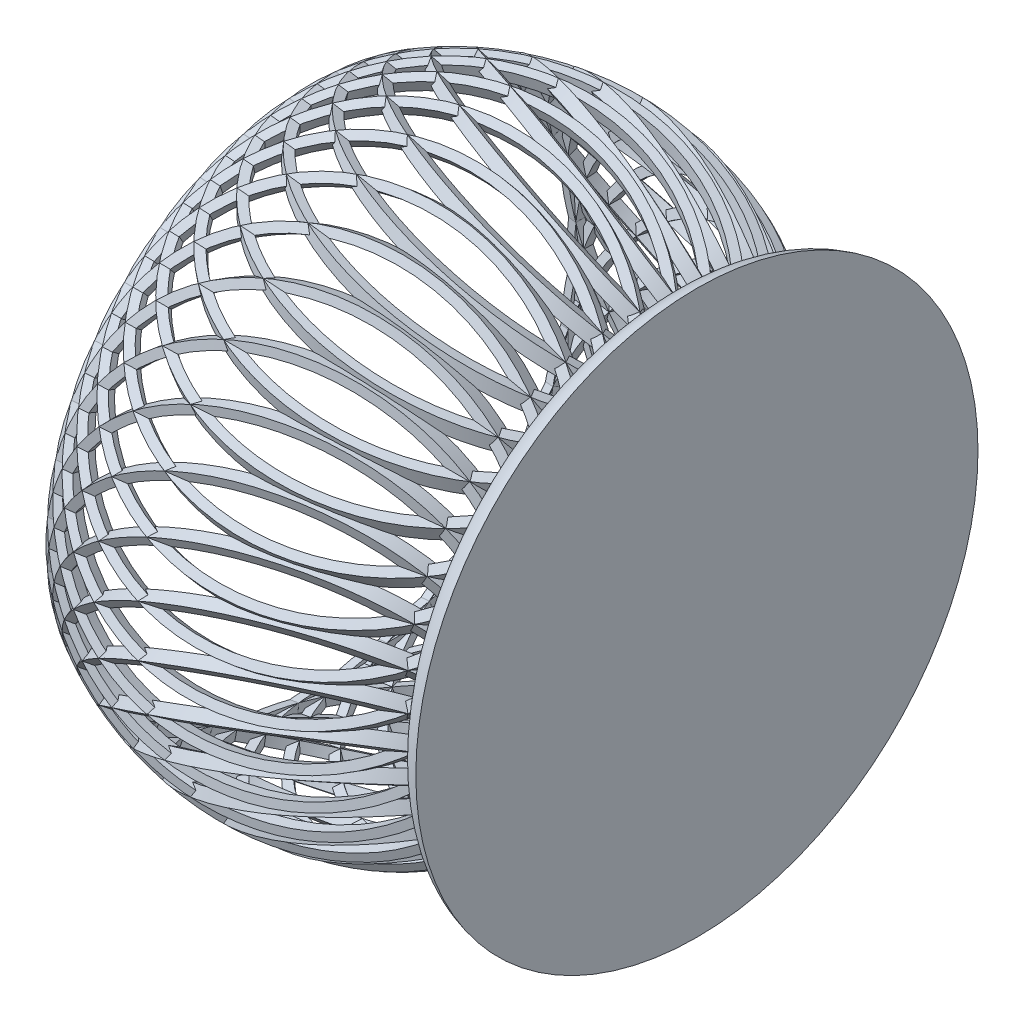
SolidWorks part; units mm, degrees
ref_plane "Front Plane" through (0, 0, 0) normal (0, 0, 1) x (1, 0, 0)
ref_plane "Top Plane" through (0, 0, 0) normal (0, 1, 0) x (1, 0, 0)
ref_plane "Right Plane" through (0, 0, 0) normal (1, 0, 0) x (0, 0, -1)
sketch "Sketch1" plane through (0, 0, 0) normal (0, 0, 1) x (1, 0, 0)
  circle A0 centre (0, 0) radius 40
  dimension "D1" = 80
extrude "Extrude-Thin1" add sketch "Sketch1" against normal blind 120 thin thin type one direction wall 2
sketch "Sketch3" plane through (0, 0, 0) normal (0, 1, 0) x (1, 0, 0)
  line L0 (-42, 120) -> (-42, 0) construction
  line L1 (42, 0) -> (42, 120) construction
  line L2 (-42, 62) -> (-42, 60)
  line L3 (42, 32.1832) -> (42, 35.1832)
  line L4 (-42, 0) -> (42, 0) construction
  arc A0 (-42, 60) -> (42, 32.1832) centre (-77.3505, -187.4881) cw
  arc A1 (-42, 62) -> (42, 35.1832) centre (-68.6517, -166.4506) cw
  dimension "D1" = 250
  dimension "D2" = 230
  dimension "D3" = 2
  dimension "D4" = 3
  dimension "D5" = 60
extrude "Cut-Extrude1" cut sketch "Sketch3" against normal through all both and the other way through all flip side to cut
sketch "Sketch4" plane through (0, 0, 0) normal (0, 1, 0) x (1, 0, 0)
  line L0 (0, 0) -> (-69.5363, 0) construction
pattern_circular "CirPattern1" count 4 over 360 about axis through (0, 0, 0) along (-1, 0, 0) reverse direction yes of bodies 102
pattern_circular "CirPattern2" count 9 over 360 about axis through (0, 0, 0) along (-1, 0, 0) of bodies 105 104 103 102
sketch "Sketch5" plane through (0, 0, 0) normal (0, 1, 0) x (1, 0, 0)
  line L0 (42, 0) -> (42, 56.4467)
  line L1 (48.3227, 65.7688) -> (48.3227, 0)
  line L2 (48.3227, 0) -> (42, 0)
  line L3 (42, 0) -> (-76.3996, 0) construction
  circle A0 centre (0, 0) radius 42 construction
  arc A1 (42, 56.4467) -> (48.3227, 65.7688) centre (49.8224, 57.9464) cw
revolve "Revolve1" add sketch "Sketch5" angle 360 about L3
